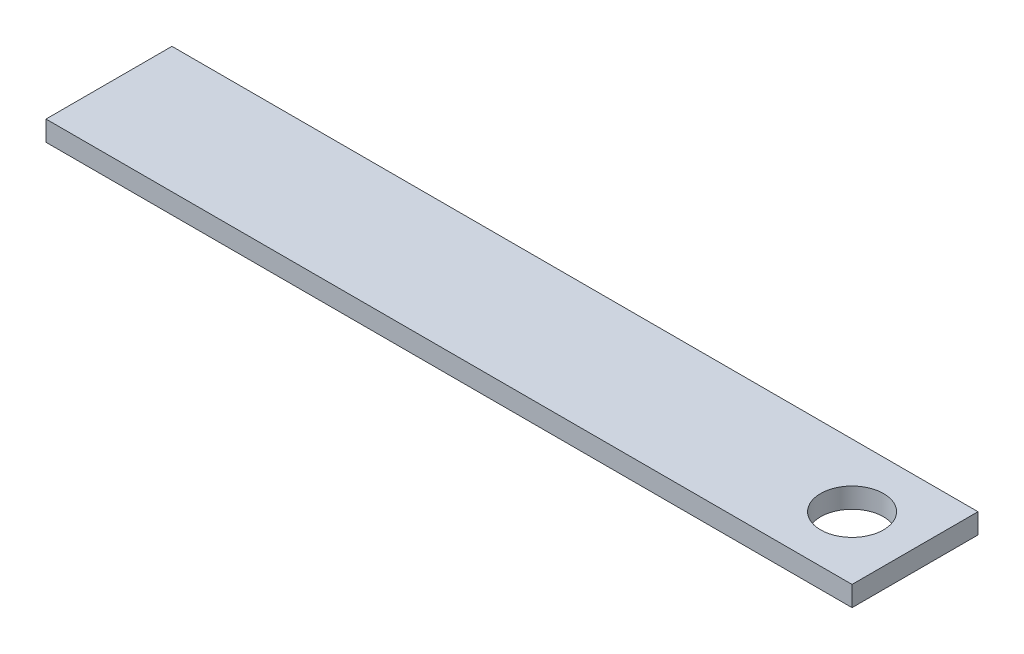
SolidWorks part; units mm, degrees
ref_plane "Front Plane" through (0, 0, 0) normal (0, 0, 1) x (1, 0, 0)
ref_plane "Top Plane" through (0, 0, 0) normal (0, 1, 0) x (1, 0, 0)
ref_plane "Right Plane" through (0, 0, 0) normal (1, 0, 0) x (0, 0, -1)
sketch "Sketch1" plane through (0, 0, 0) normal (0, 1, 0) x (1, 0, 0)
  line L1 (-80, 12.5) -> (80, 12.5)
  line L2 (-80, 12.5) -> (-80, -12.5)
  line L3 (-80, -12.5) -> (80, -12.5)
  line L4 (80, 12.5) -> (80, -12.5)
  line L5 (-80, 12.5) -> (80, -12.5) construction
  line L6 (-80, -12.5) -> (80, 12.5) construction
  circle A4 centre (67.5, 0) radius 6.25
  point P0 (0, 0)
  point P17 (80, 0)
  dimension "D3" = 12.5
  dimension "D4" = 12.5
  dimension "D1" = 25
  dimension "D2" = 160
extrude "Boss-Extrude1" add sketch "Sketch1" along normal blind 4 contours L3 L4 L1 L2 A4 | L3 region at (-2.1364, 0, 0)
